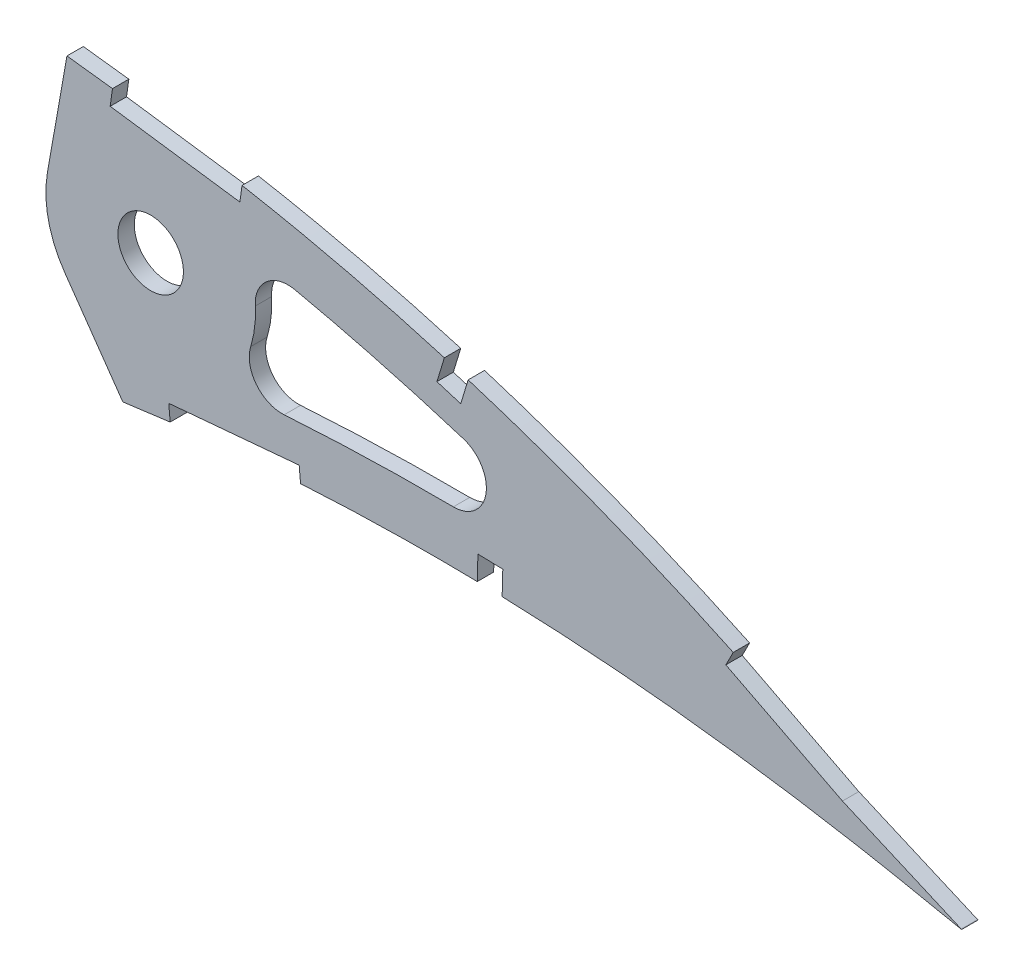
SolidWorks part; units mm, degrees
material "Pine"
ref_plane "Front Plane" through (0, 0, 0) normal (0, 0, 1) x (1, 0, 0)
ref_plane "Top Plane" through (0, 0, 0) normal (0, 1, 0) x (1, 0, 0)
ref_plane "Right Plane" through (0, 0, 0) normal (1, 0, 0) x (0, 0, -1)
curve "Curve2"
curve "Curve3"
sketch "Sketch1" plane through (0, 0, 0) normal (0, 0, 1) x (1, 0, 0)
  line L1 (519.5802, -0.8111) -> (524.4049, -1.7687)
  line L2 (520.229, 0.8111) -> (524.4049, -1.7687)
  spline S0 degree 3 poles (-2903.7635, -749.124) (66.2436, 68.8235) (-8.6937, 20.855) (1.129, -3.7148) (2.0912, -5.4642) (3.3081, -7.1386) (4.7718, -8.7374) (6.479, -10.2623) (8.428, -11.7125) (10.6162, -13.0874) (13.0406, -14.3883) (15.6982, -15.6145) (18.5868, -16.7656) (21.7032, -17.8401) (25.0435, -18.8396) (28.6046, -19.7616) (32.3825, -20.6074) (36.3735, -21.375) (40.5732, -22.065) (44.9774, -22.6771) (49.5814, -23.2117) (54.3808, -23.6676) (59.3708, -24.0458) (64.5464, -24.3466) (69.9027, -24.5709) (75.4344, -24.718) (81.1363, -24.7899) (87.003, -24.788) (93.0289, -24.7115) (99.2088, -24.5648) (105.5368, -24.3469) (112.0073, -24.0604) (118.6142, -23.7083) (125.3518, -23.2917) (132.2141, -22.8125) (139.1951, -22.2745) (146.2885, -21.679) (153.4882, -21.0296) (160.7876, -20.3295) (168.1806, -19.5808) (175.6606, -18.7872) (183.2209, -17.9512) (190.8551, -17.0772) (198.5563, -16.1668) (206.3179, -15.2253) (214.1326, -14.2544) (221.9939, -13.2579) (229.8947, -12.2404) (237.8276, -11.2019) (245.786, -10.1497) (253.7621, -9.0829) (261.7491, -8.0072) (269.7395, -6.9257) (277.7256, -5.8389) (285.7003, -4.7513) (293.6562, -3.6657) (301.5856, -2.5824) (309.4812, -1.5067) (317.3352, -0.4385) (325.1402, 0.6201) (332.8888, 1.6659) (340.5737, 2.6975) (348.187, 3.7144) (355.721, 4.7168) (363.0553, 5.6745) (370.1707, 6.6383) (377.0913, 7.4284) (383.9258, 8.1028) (390.6811, 8.6557) (397.3493, 9.0951) (403.9227, 9.4241) (410.3934, 9.6473) (416.7532, 9.7713) (422.9943, 9.7993) (429.1081, 9.7402) (435.0867, 9.5987) (440.9216, 9.3813) (446.6049, 9.0952) (452.1283, 8.7483) (457.4837, 8.3456) (462.6634, 7.8966) (467.6597, 7.4078) (472.4647, 6.8849) (477.0715, 6.3387) (481.4727, 5.7729) (485.6616, 5.1968) (489.6316, 4.6162) (493.3764, 4.0385) (496.89, 3.4693) (500.1667, 2.916) (503.2016, 2.384) (505.9892, 1.8782) (508.5257, 1.4052) (510.8062, 0.9673) (512.8275, 0.5717) (514.5859, 0.2202) (516.0789, -0.0824) (517.3037, -0.3347) (518.2586, -0.5328) (518.9417, -0.6767) (537.0698, -4.4604) (553.3394, -15.9066) (1193.1482, 2921.6684) knots -0.137857 -0.137857 -0.137857 -0.137857 0.003638 0.007293 0.011028 0.014901 0.018963 0.023258 0.027821 0.032679 0.037853 0.043362 0.049215 0.055422 0.061989 0.068918 0.076211 0.083868 0.091887 0.100266 0.109 0.118085 0.127515 0.137285 0.147388 0.157816 0.168563 0.179619 0.190977 0.202627 0.21456 0.226767 0.239236 0.251959 0.264924 0.27812 0.291536 0.30516 0.318981 0.332985 0.347163 0.361499 0.375981 0.390597 0.405333 0.420175 0.43511 0.450124 0.465203 0.480333 0.495501 0.51069 0.525887 0.541078 0.556247 0.571382 0.586466 0.601485 0.616424 0.631269 0.646007 0.660621 0.675098 0.689423 0.703582 0.716908 0.730009 0.742952 0.755726 0.76832 0.780724 0.792927 0.804916 0.816679 0.828204 0.839475 0.850481 0.861208 0.871639 0.881763 0.891564 0.901027 0.910139 0.918884 0.927249 0.935221 0.942785 0.949928 0.956638 0.962904 0.968712 0.974054 0.978918 0.983297 0.98718 0.990561 0.993433 0.995791 0.99763 0.998946 0.999737 1.102307 1.102307 1.102307 1.102307 only from (0, 0) to (519.5802, -0.8111) construction
  spline S1 degree 3 poles (2144.5607, 2521.6799) (550.9976, -26.3511) (537.2872, -9.6513) (519.6711, 1.1542) (519.0735, 1.5208) (518.237, 2.0313) (517.1622, 2.6844) (515.8486, 3.4756) (514.2969, 4.4021) (512.5075, 5.4598) (510.4807, 6.6436) (508.2172, 7.9486) (505.7172, 9.3676) (502.9816, 10.8948) (500.0114, 12.5227) (496.8072, 14.2443) (493.3701, 16.0505) (489.7015, 17.9338) (485.8019, 19.8836) (481.6733, 21.8919) (477.317, 23.9487) (472.7345, 26.0429) (467.9284, 28.1661) (462.9001, 30.305) (457.6524, 32.4505) (452.1876, 34.5902) (446.5089, 36.7144) (440.6184, 38.8094) (434.5207, 40.866) (428.2186, 42.8708) (421.7166, 44.813) (415.0186, 46.68) (408.1302, 48.4622) (401.0555, 50.1466) (393.8008, 51.7219) (386.3718, 53.1787) (378.7746, 54.5024) (371.0303, 55.692) (363.2636, 56.6815) (355.5128, 57.652) (347.7736, 58.5637) (339.9398, 59.4368) (332.019, 60.2663) (324.019, 61.0497) (315.9478, 61.7836) (307.814, 62.4658) (299.6253, 63.0925) (291.3904, 63.6628) (283.1174, 64.1714) (274.8152, 64.6183) (266.4922, 65.0001) (258.157, 65.3142) (249.8185, 65.5589) (241.4854, 65.7316) (233.1666, 65.8314) (224.8708, 65.8555) (216.6071, 65.8035) (208.384, 65.6736) (200.2107, 65.464) (192.0958, 65.1743) (184.048, 64.8046) (176.0762, 64.3519) (168.189, 63.8191) (160.3952, 63.2038) (152.7034, 62.506) (145.1216, 61.7286) (137.6583, 60.8693) (130.3214, 59.9308) (123.1191, 58.9147) (116.0593, 57.8206) (109.1496, 56.6517) (102.3976, 55.409) (95.8102, 54.0963) (89.3948, 52.714) (83.1581, 51.266) (77.1065, 49.7551) (71.2467, 48.1838) (65.5845, 46.5561) (60.1256, 44.8756) (54.8764, 43.1442) (49.8409, 41.3683) (45.0253, 39.5493) (40.4333, 37.6928) (36.0702, 35.8014) (31.9393, 33.8806) (28.0452, 31.9329) (24.3908, 29.9636) (20.9797, 27.9757) (17.8153, 25.973) (14.8987, 23.9604) (12.2341, 21.9394) (9.8224, 19.9149) (7.6651, 17.8901) (5.7652, 15.8664) (4.1228, 13.8473) (2.7399, 11.8344) (1.6168, 9.8297) (0.7561, 7.8345) (0.1568, 5.85) (-0.1712, 3.8792) (-1.2714, -22.5145) (85.5395, -42.7616) (-2987.8188, -259.5241) knots -0.109813 -0.109813 -0.109813 -0.109813 0.000254 0.001015 0.002283 0.004057 0.006331 0.009105 0.012374 0.016134 0.02038 0.025106 0.030306 0.035972 0.0421 0.048678 0.055702 0.06316 0.071046 0.07935 0.088063 0.097176 0.106678 0.116562 0.126814 0.137428 0.148394 0.1597 0.171338 0.183298 0.19557 0.208144 0.221012 0.234162 0.247587 0.261277 0.275223 0.289414 0.303771 0.317689 0.331784 0.34604 0.360444 0.374983 0.38964 0.404403 0.419257 0.434187 0.449177 0.464215 0.479284 0.49437 0.509458 0.524532 0.539579 0.554583 0.56953 0.584403 0.599191 0.613877 0.628447 0.642889 0.657186 0.671326 0.685294 0.699078 0.712665 0.726043 0.739198 0.752118 0.764792 0.777208 0.789356 0.801224 0.812804 0.824083 0.835055 0.84571 0.856038 0.866034 0.875689 0.884998 0.893953 0.902553 0.910789 0.918661 0.926166 0.933303 0.940071 0.946475 0.952518 0.958205 0.963547 0.968557 0.97325 0.977651 0.981787 0.985694 0.989415 0.993001 0.996508 1.132043 1.132043 1.132043 1.132043 only from (520.229, 0.8111) to (0, 0) construction
  spline S2 degree 3 poles (0, 0) (0.1336, -0.6306) (0.4014, -1.8948) (1.129, -3.7148) (2.0912, -5.4642) (3.3081, -7.1386) (4.7718, -8.7374) (6.479, -10.2623) (8.428, -11.7125) (10.6162, -13.0874) (13.0406, -14.3883) (15.6982, -15.6145) (18.5868, -16.7656) (21.7032, -17.8401) (25.0435, -18.8396) (28.6046, -19.7616) (32.3825, -20.6074) (36.3735, -21.375) (40.5732, -22.065) (44.9774, -22.6771) (49.5814, -23.2117) (54.3808, -23.6676) (59.3708, -24.0458) (64.5464, -24.3466) (69.9027, -24.5709) (75.4344, -24.718) (81.1363, -24.7899) (87.003, -24.788) (93.0289, -24.7115) (99.2088, -24.5648) (105.5368, -24.3469) (112.0073, -24.0604) (118.6142, -23.7083) (125.3518, -23.2917) (132.2141, -22.8125) (139.1951, -22.2745) (146.2885, -21.679) (153.4882, -21.0296) (160.7876, -20.3295) (168.1806, -19.5808) (175.6606, -18.7872) (183.2209, -17.9512) (190.8551, -17.0772) (198.5563, -16.1668) (206.3179, -15.2253) (214.1326, -14.2544) (221.9939, -13.2579) (229.8947, -12.2404) (237.8276, -11.2019) (245.786, -10.1497) (253.7621, -9.0829) (261.7491, -8.0072) (269.7395, -6.9257) (277.7256, -5.8389) (285.7003, -4.7513) (293.6562, -3.6657) (301.5856, -2.5824) (309.4812, -1.5067) (317.3352, -0.4385) (325.1402, 0.6201) (332.8888, 1.6659) (340.5737, 2.6975) (348.187, 3.7144) (355.721, 4.7168) (363.0553, 5.6745) (370.1707, 6.6383) (377.0913, 7.4284) (383.9258, 8.1028) (390.6811, 8.6557) (397.3493, 9.0951) (403.9227, 9.4241) (410.3934, 9.6473) (416.7532, 9.7713) (422.9943, 9.7993) (429.1081, 9.7402) (435.0867, 9.5987) (440.9216, 9.3813) (446.6049, 9.0952) (452.1283, 8.7483) (457.4837, 8.3456) (462.6634, 7.8966) (467.6597, 7.4078) (472.4647, 6.8849) (477.0715, 6.3387) (481.4727, 5.7729) (485.6616, 5.1968) (489.6316, 4.6162) (493.3764, 4.0385) (496.89, 3.4693) (500.1667, 2.916) (503.2016, 2.384) (505.9892, 1.8782) (508.5257, 1.4052) (510.8062, 0.9673) (512.8275, 0.5717) (514.5859, 0.2202) (516.0789, -0.0824) (517.3037, -0.3347) (518.2586, -0.5328) (518.9417, -0.6767) (519.3522, -0.7624) (519.5346, -0.8013) (519.5802, -0.8111) knots 0 0 0 0 0.003638 0.007293 0.011028 0.014901 0.018963 0.023258 0.027821 0.032679 0.037853 0.043362 0.049215 0.055422 0.061989 0.068918 0.076211 0.083868 0.091887 0.100266 0.109 0.118085 0.127515 0.137285 0.147388 0.157816 0.168563 0.179619 0.190977 0.202627 0.21456 0.226767 0.239236 0.251959 0.264924 0.27812 0.291536 0.30516 0.318981 0.332985 0.347163 0.361499 0.375981 0.390597 0.405333 0.420175 0.43511 0.450124 0.465203 0.480333 0.495501 0.51069 0.525887 0.541078 0.556247 0.571382 0.586466 0.601485 0.616424 0.631269 0.646007 0.660621 0.675098 0.689423 0.703582 0.716908 0.730009 0.742952 0.755726 0.76832 0.780724 0.792927 0.804916 0.816679 0.828204 0.839475 0.850481 0.861208 0.871639 0.881763 0.891564 0.901027 0.910139 0.918884 0.927249 0.935221 0.942785 0.949928 0.956638 0.962904 0.968712 0.974054 0.978918 0.983297 0.98718 0.990561 0.993433 0.995791 0.99763 0.998946 0.999737 1 1 1 1
  spline S3 degree 3 poles (520.229, 0.8111) (520.1892, 0.8357) (520.0299, 0.9341) (519.6711, 1.1542) (519.0735, 1.5208) (518.237, 2.0313) (517.1622, 2.6844) (515.8486, 3.4756) (514.2969, 4.4021) (512.5075, 5.4598) (510.4807, 6.6436) (508.2172, 7.9486) (505.7172, 9.3676) (502.9816, 10.8948) (500.0114, 12.5227) (496.8072, 14.2443) (493.3701, 16.0505) (489.7015, 17.9338) (485.8019, 19.8836) (481.6733, 21.8919) (477.317, 23.9487) (472.7345, 26.0429) (467.9284, 28.1661) (462.9001, 30.305) (457.6524, 32.4505) (452.1876, 34.5902) (446.5089, 36.7144) (440.6184, 38.8094) (434.5207, 40.866) (428.2186, 42.8708) (421.7166, 44.813) (415.0186, 46.68) (408.1302, 48.4622) (401.0555, 50.1466) (393.8008, 51.7219) (386.3718, 53.1787) (378.7746, 54.5024) (371.0303, 55.692) (363.2636, 56.6815) (355.5128, 57.652) (347.7736, 58.5637) (339.9398, 59.4368) (332.019, 60.2663) (324.019, 61.0497) (315.9478, 61.7836) (307.814, 62.4658) (299.6253, 63.0925) (291.3904, 63.6628) (283.1174, 64.1714) (274.8152, 64.6183) (266.4922, 65.0001) (258.157, 65.3142) (249.8185, 65.5589) (241.4854, 65.7316) (233.1666, 65.8314) (224.8708, 65.8555) (216.6071, 65.8035) (208.384, 65.6736) (200.2107, 65.464) (192.0958, 65.1743) (184.048, 64.8046) (176.0762, 64.3519) (168.189, 63.8191) (160.3952, 63.2038) (152.7034, 62.506) (145.1216, 61.7286) (137.6583, 60.8693) (130.3214, 59.9308) (123.1191, 58.9147) (116.0593, 57.8206) (109.1496, 56.6517) (102.3976, 55.409) (95.8102, 54.0963) (89.3948, 52.714) (83.1581, 51.266) (77.1065, 49.7551) (71.2467, 48.1838) (65.5845, 46.5561) (60.1256, 44.8756) (54.8764, 43.1442) (49.8409, 41.3683) (45.0253, 39.5493) (40.4333, 37.6928) (36.0702, 35.8014) (31.9393, 33.8806) (28.0452, 31.9329) (24.3908, 29.9636) (20.9797, 27.9757) (17.8153, 25.973) (14.8987, 23.9604) (12.2341, 21.9394) (9.8224, 19.9149) (7.6651, 17.8901) (5.7652, 15.8664) (4.1228, 13.8473) (2.7399, 11.8344) (1.6168, 9.8297) (0.7561, 7.8345) (0.1568, 5.85) (-0.1712, 3.8792) (-0.2528, 1.9205) (-0.0842, 0.6392) (0, 0) knots 0 0 0 0 0.000254 0.001015 0.002283 0.004057 0.006331 0.009105 0.012374 0.016134 0.02038 0.025106 0.030306 0.035972 0.0421 0.048678 0.055702 0.06316 0.071046 0.07935 0.088063 0.097176 0.106678 0.116562 0.126814 0.137428 0.148394 0.1597 0.171338 0.183298 0.19557 0.208144 0.221012 0.234162 0.247587 0.261277 0.275223 0.289414 0.303771 0.317689 0.331784 0.34604 0.360444 0.374983 0.38964 0.404403 0.419257 0.434187 0.449177 0.464215 0.479284 0.49437 0.509458 0.524532 0.539579 0.554583 0.56953 0.584403 0.599191 0.613877 0.628447 0.642889 0.657186 0.671326 0.685294 0.699078 0.712665 0.726043 0.739198 0.752118 0.764792 0.777208 0.789356 0.801224 0.812804 0.824083 0.835055 0.84571 0.856038 0.866034 0.875689 0.884998 0.893953 0.902553 0.910789 0.918661 0.926166 0.933303 0.940071 0.946475 0.952518 0.958205 0.963547 0.968557 0.97325 0.977651 0.981787 0.985694 0.989415 0.993001 0.996508 1 1 1 1
extrude "Boss-Extrude1" add sketch "Sketch1" along normal blind 3.175
sketch "Sketch4" plane through (0, 0, 0) normal (0, 0, -1) x (-1, 0, 0)
  line L0 (-347.1309, 36.7611) -> (-350.9097, 58.1919)
  line L1 (-350.497, 21.5775) -> (-361.7496, 5.5072)
  line L2 (-367.1422, 33.2326) -> (-406.863, 33.2326)
  circle A0 centre (-367.1422, 33.2326) radius 20.32
  circle A1 centre (-367.1422, 33.2326) radius 6.35
  spline S2 degree 3 poles (1939.7558, -484.7932) (-49.4812, 57.6608) (7.5449, 17.9816) (-1.129, -3.7148) (-2.0912, -5.4642) (-3.3081, -7.1386) (-4.7718, -8.7374) (-6.479, -10.2623) (-8.428, -11.7125) (-10.6162, -13.0874) (-13.0406, -14.3883) (-15.6982, -15.6145) (-18.5868, -16.7656) (-21.7032, -17.8401) (-25.0435, -18.8396) (-28.6046, -19.7616) (-32.3825, -20.6074) (-36.3735, -21.375) (-40.5732, -22.065) (-44.9774, -22.6771) (-49.5814, -23.2117) (-54.3808, -23.6676) (-59.3708, -24.0458) (-64.5464, -24.3466) (-69.9027, -24.5709) (-75.4344, -24.718) (-81.1363, -24.7899) (-87.003, -24.788) (-93.0289, -24.7115) (-99.2088, -24.5648) (-105.5368, -24.3469) (-112.0073, -24.0604) (-118.6142, -23.7083) (-125.3518, -23.2917) (-132.2141, -22.8125) (-139.1951, -22.2745) (-146.2885, -21.679) (-153.4882, -21.0296) (-160.7876, -20.3295) (-168.1806, -19.5808) (-175.6606, -18.7872) (-183.2209, -17.9512) (-190.8551, -17.0772) (-198.5563, -16.1668) (-206.3179, -15.2253) (-214.1326, -14.2544) (-221.9939, -13.2579) (-229.8947, -12.2404) (-237.8276, -11.2019) (-245.786, -10.1497) (-253.7621, -9.0829) (-261.7491, -8.0072) (-269.7395, -6.9257) (-277.7256, -5.8389) (-285.7003, -4.7513) (-293.6562, -3.6657) (-301.5856, -2.5824) (-309.4812, -1.5067) (-317.3352, -0.4385) (-325.1402, 0.6201) (-332.8888, 1.6659) (-340.5737, 2.6975) (-348.187, 3.7144) (-355.721, 4.7168) (-363.0553, 5.6745) (-370.1707, 6.6383) (-377.0913, 7.4284) (-383.9258, 8.1028) (-390.6811, 8.6557) (-397.3493, 9.0951) (-403.9227, 9.4241) (-410.3934, 9.6473) (-416.7532, 9.7713) (-422.9943, 9.7993) (-429.1081, 9.7402) (-435.0867, 9.5987) (-440.9216, 9.3813) (-446.6049, 9.0952) (-452.1283, 8.7483) (-457.4837, 8.3456) (-462.6634, 7.8966) (-467.6597, 7.4078) (-472.4647, 6.8849) (-477.0715, 6.3387) (-481.4727, 5.7729) (-485.6616, 5.1968) (-489.6316, 4.6162) (-493.3764, 4.0385) (-496.89, 3.4693) (-500.1667, 2.916) (-503.2016, 2.384) (-505.9892, 1.8782) (-508.5257, 1.4052) (-510.8062, 0.9673) (-512.8275, 0.5717) (-514.5859, 0.2202) (-516.0789, -0.0824) (-517.3037, -0.3347) (-518.2586, -0.5328) (-518.9417, -0.6767) (-534.8295, -3.9928) (-549.2415, -13.1623) (-979.5797, 1945.0117) knots -0.120445 -0.120445 -0.120445 -0.120445 0.003638 0.007293 0.011028 0.014901 0.018963 0.023258 0.027821 0.032679 0.037853 0.043362 0.049215 0.055422 0.061989 0.068918 0.076211 0.083868 0.091887 0.100266 0.109 0.118085 0.127515 0.137285 0.147388 0.157816 0.168563 0.179619 0.190977 0.202627 0.21456 0.226767 0.239236 0.251959 0.264924 0.27812 0.291536 0.30516 0.318981 0.332985 0.347163 0.361499 0.375981 0.390597 0.405333 0.420175 0.43511 0.450124 0.465203 0.480333 0.495501 0.51069 0.525887 0.541078 0.556247 0.571382 0.586466 0.601485 0.616424 0.631269 0.646007 0.660621 0.675098 0.689423 0.703582 0.716908 0.730009 0.742952 0.755726 0.76832 0.780724 0.792927 0.804916 0.816679 0.828204 0.839475 0.850481 0.861208 0.871639 0.881763 0.891564 0.901027 0.910139 0.918884 0.927249 0.935221 0.942785 0.949928 0.956638 0.962904 0.968712 0.974054 0.978918 0.983297 0.98718 0.990561 0.993433 0.995791 0.99763 0.998946 0.999737 1.089371 1.089371 1.089371 1.089371 only from (0, 0) to (-519.5802, -0.8111) construction
  spline S3 degree 3 poles (-1613.7482, 1674.6901) (-547.5042, -22.2613) (-535.1053, -8.313) (-519.6711, 1.1542) (-519.0735, 1.5208) (-518.237, 2.0313) (-517.1622, 2.6844) (-515.8486, 3.4756) (-514.2969, 4.4021) (-512.5075, 5.4598) (-510.4807, 6.6436) (-508.2172, 7.9486) (-505.7172, 9.3676) (-502.9816, 10.8948) (-500.0114, 12.5227) (-496.8072, 14.2443) (-493.3701, 16.0505) (-489.7015, 17.9338) (-485.8019, 19.8836) (-481.6733, 21.8919) (-477.317, 23.9487) (-472.7345, 26.0429) (-467.9284, 28.1661) (-462.9001, 30.305) (-457.6524, 32.4505) (-452.1876, 34.5902) (-446.5089, 36.7144) (-440.6184, 38.8094) (-434.5207, 40.866) (-428.2186, 42.8708) (-421.7166, 44.813) (-415.0186, 46.68) (-408.1302, 48.4622) (-401.0555, 50.1466) (-393.8008, 51.7219) (-386.3718, 53.1787) (-378.7746, 54.5024) (-371.0303, 55.692) (-363.2636, 56.6815) (-355.5128, 57.652) (-347.7736, 58.5637) (-339.9398, 59.4368) (-332.019, 60.2663) (-324.019, 61.0497) (-315.9478, 61.7836) (-307.814, 62.4658) (-299.6253, 63.0925) (-291.3904, 63.6628) (-283.1174, 64.1714) (-274.8152, 64.6183) (-266.4922, 65.0001) (-258.157, 65.3142) (-249.8185, 65.5589) (-241.4854, 65.7316) (-233.1666, 65.8314) (-224.8708, 65.8555) (-216.6071, 65.8035) (-208.384, 65.6736) (-200.2107, 65.464) (-192.0958, 65.1743) (-184.048, 64.8046) (-176.0762, 64.3519) (-168.189, 63.8191) (-160.3952, 63.2038) (-152.7034, 62.506) (-145.1216, 61.7286) (-137.6583, 60.8693) (-130.3214, 59.9308) (-123.1191, 58.9147) (-116.0593, 57.8206) (-109.1496, 56.6517) (-102.3976, 55.409) (-95.8102, 54.0963) (-89.3948, 52.714) (-83.1581, 51.266) (-77.1065, 49.7551) (-71.2467, 48.1838) (-65.5845, 46.5561) (-60.1256, 44.8756) (-54.8764, 43.1442) (-49.8409, 41.3683) (-45.0253, 39.5493) (-40.4333, 37.6928) (-36.0702, 35.8014) (-31.9393, 33.8806) (-28.0452, 31.9329) (-24.3908, 29.9636) (-20.9797, 27.9757) (-17.8153, 25.973) (-14.8987, 23.9604) (-12.2341, 21.9394) (-9.8224, 19.9149) (-7.6651, 17.8901) (-5.7652, 15.8664) (-4.1228, 13.8473) (-2.7399, 11.8344) (-1.6168, 9.8297) (-0.7561, 7.8345) (-0.1568, 5.85) (0.1712, 3.8792) (1.1427, -19.4272) (-65.9725, -37.8239) (1990.4087, -188.0581) knots -0.095928 -0.095928 -0.095928 -0.095928 0.000254 0.001015 0.002283 0.004057 0.006331 0.009105 0.012374 0.016134 0.02038 0.025106 0.030306 0.035972 0.0421 0.048678 0.055702 0.06316 0.071046 0.07935 0.088063 0.097176 0.106678 0.116562 0.126814 0.137428 0.148394 0.1597 0.171338 0.183298 0.19557 0.208144 0.221012 0.234162 0.247587 0.261277 0.275223 0.289414 0.303771 0.317689 0.331784 0.34604 0.360444 0.374983 0.38964 0.404403 0.419257 0.434187 0.449177 0.464215 0.479284 0.49437 0.509458 0.524532 0.539579 0.554583 0.56953 0.584403 0.599191 0.613877 0.628447 0.642889 0.657186 0.671326 0.685294 0.699078 0.712665 0.726043 0.739198 0.752118 0.764792 0.777208 0.789356 0.801224 0.812804 0.824083 0.835055 0.84571 0.856038 0.866034 0.875689 0.884998 0.893953 0.902553 0.910789 0.918661 0.926166 0.933303 0.940071 0.946475 0.952518 0.958205 0.963547 0.968557 0.97325 0.977651 0.981787 0.985694 0.989415 0.993001 0.996508 1.11536 1.11536 1.11536 1.11536 only from (-520.229, 0.8111) to (0, 0) construction
  spline S4 degree 3 poles (-1978.354, 2157.5892) (159.6529, 858.6126) (-7.0413, 13.2519) (-10.1565, 1.1414) (-10.167, 1.1042) (-10.1763, 1.0725) (-10.1781, 1.0668) (-10.1835, 1.0497) (-10.1867, 1.0399) (-10.2052, 0.985) (-10.2286, 0.9219) (-10.2791, 0.8017) (-10.2985, 0.7574) (-10.3426, 0.661) (-10.3676, 0.6085) (-10.4428, 0.4561) (-10.496, 0.3558) (-10.6081, 0.1584) (-10.6662, 0.0627) (-10.855, -0.2291) (-11.0064, -0.4384) (-11.5378, -1.0936) (-11.9971, -1.5677) (-13.099, -2.5256) (-13.7412, -3.01) (-15.1702, -3.9568) (-15.9588, -4.4208) (-17.636, -5.3094) (-18.5262, -5.7351) (-21.3094, -6.9503) (-23.3073, -7.6749) (-27.467, -8.9758) (-29.6229, -9.5497) (-34.0316, -10.5753) (-36.2795, -11.0252) (-40.839, -11.8243) (-43.1471, -12.1728) (-47.8035, -12.7862) (-50.1501, -13.0508) (-57.2292, -13.7373) (-62.003, -14.0541) (-71.5985, -14.4809) (-76.422, -14.5891) (-83.6816, -14.6324) (-86.1037, -14.6268) (-90.9551, -14.5789) (-93.3856, -14.5371) (-100.6793, -14.3647) (-105.548, -14.1854) (-120.1773, -13.4939) (-129.9476, -12.83) (-149.5009, -11.2301) (-159.287, -10.2936) (-178.863, -8.2392) (-188.6532, -7.1203) (-203.3458, -5.3542) (-208.2424, -4.7511) (-218.0387, -3.5207) (-222.9395, -2.8943) (-232.7359, -1.6243) (-237.6385, -0.9795) (-247.4393, 0.3202) (-252.3404, 0.9774) (-262.147, 2.2986) (-267.05, 2.9625) (-276.8577, 4.2964) (-281.7641, 4.9659) (-291.5768, 6.3047) (-296.4825, 6.9752) (-306.3007, 8.3142) (-311.2087, 8.9822) (-325.9378, 10.9826) (-335.766, 12.3068) (-348.0467, 13.9451) (-350.5039, 14.2725) (-354.1964, 14.7609) (-355.4285, 14.923) (-357.8843, 15.2457) (-359.1092, 15.4066) (-361.5526, 15.7296) (-362.7689, 15.8922) (-365.2348, 16.221) (-366.4798, 16.3859) (-368.3663, 16.6273) (-368.9995, 16.7068) (-371.53, 17.0174) (-373.424, 17.2342) (-377.8329, 17.7104) (-380.3527, 17.9617) (-385.4072, 18.4196) (-387.9354, 18.6255) (-395.5221, 19.1767) (-400.5883, 19.4552) (-408.19, 19.7386) (-410.7237, 19.8108) (-415.7936, 19.9113) (-418.3301, 19.9392) (-425.9339, 19.9566) (-431.0019, 19.8815) (-441.1324, 19.5579) (-446.1907, 19.3102) (-453.7725, 18.8139) (-456.2982, 18.6271) (-775.6257, -7.5609) (-1062.3017, -351.5368) (-2984.1092, -1609.9578) knots -0.216436 -0.216436 -0.216436 -0.216436 0.001953 0.001953 0.00293 0.00293 0.003418 0.003418 0.003906 0.003906 0.005859 0.005859 0.006836 0.006836 0.007813 0.007813 0.009766 0.009766 0.011719 0.011719 0.015625 0.015625 0.023438 0.023438 0.03125 0.03125 0.039063 0.039063 0.046875 0.046875 0.0625 0.0625 0.078125 0.078125 0.09375 0.09375 0.109375 0.109375 0.125 0.125 0.15625 0.15625 0.1875 0.1875 0.203125 0.203125 0.21875 0.21875 0.25 0.25 0.3125 0.3125 0.375 0.375 0.4375 0.4375 0.46875 0.46875 0.5 0.5 0.53125 0.53125 0.5625 0.5625 0.59375 0.59375 0.625 0.625 0.65625 0.65625 0.6875 0.6875 0.75 0.75 0.765625 0.765625 0.773438 0.773438 0.78125 0.78125 0.789063 0.789063 0.796875 0.796875 0.800781 0.800781 0.8125 0.8125 0.828125 0.828125 0.84375 0.84375 0.875 0.875 0.890625 0.890625 0.90625 0.90625 0.9375 0.9375 0.96875 0.96875 0.984375 0.984375 2.947098 2.947098 2.947098 2.947098 only from (-10.022, 1.7185) to (-466.3815, 17.739)
  spline S5 degree 3 poles (-2960.1923, -1647.6146) (-778.0163, -316.2747) (-661.2066, -63.7231) (-457.1185, 21.6971) (-454.7864, 22.6463) (-450.1039, 24.4978) (-447.7524, 25.4007) (-443.0352, 27.1579) (-440.669, 28.0121) (-428.7885, 32.1652) (-419.1573, 35.0991) (-404.5516, 38.8923) (-399.6593, 40.0545) (-392.2853, 41.6432) (-389.8214, 42.1473) (-384.8862, 43.1026) (-382.4148, 43.5535) (-377.456, 44.4051) (-374.9691, 44.8071) (-371.8706, 45.272) (-371.2512, 45.3631) (-370.0129, 45.5414) (-369.3949, 45.6283) (-367.531, 45.885) (-365.6514, 46.1331) (-363.7495, 46.3759) (-362.4766, 46.5374) (-361.8369, 46.6182) (-359.9197, 46.8599) (-358.6437, 47.0199) (-354.8218, 47.4941) (-352.2828, 47.8012) (-347.1922, 48.3982) (-344.6438, 48.6888) (-339.5477, 49.2537) (-336.9993, 49.5279) (-329.3512, 50.3256) (-324.2496, 50.8242) (-308.9368, 52.2174) (-298.7176, 53.0107) (-278.2717, 54.3039) (-268.0406, 54.8057) (-247.5801, 55.4913) (-237.3501, 55.6755) (-216.9004, 55.6922) (-206.6831, 55.5256) (-191.3779, 54.9785) (-186.2812, 54.7472) (-176.0979, 54.177) (-171.0099, 53.8396) (-160.8533, 53.0504) (-155.7814, 52.598) (-145.6574, 51.572) (-140.6072, 50.9971) (-125.4892, 49.071) (-115.4646, 47.5214) (-100.5547, 44.7064) (-95.6096, 43.687) (-85.777, 41.462) (-80.8922, 40.2578) (-71.2072, 37.6367) (-66.4068, 36.2209) (-59.3024, 33.909) (-56.9474, 33.1063) (-52.2821, 31.4343) (-49.9693, 30.5636) (-45.3927, 28.7458) (-43.1318, 27.7996) (-38.6715, 25.8196) (-36.476, 24.7882) (-32.1758, 22.6281) (-30.0692, 21.4995) (-27.0125, 19.7284) (-26.0103, 19.1247) (-24.0464, 17.889) (-23.0831, 17.2561) (-21.2128, 15.9659) (-20.3049, 15.3076) (-18.5534, 13.9629) (-17.7093, 13.2763) (-16.1081, 11.8824) (-15.3519, 11.176) (-14.3045, 10.1109) (-13.9701, 9.7552) (-13.3325, 9.0431) (-13.0296, 8.687) (-12.1803, 7.6299) (-11.6896, 6.9348) (-10.8906, 5.6128) (-10.5874, 4.9936) (-10.269, 4.158) (-10.1861, 3.8969) (-10.0953, 3.5459) (-10.0707, 3.4366) (-10.0267, 3.2104) (-10.0081, 3.096) (-9.9777, 2.8649) (-9.9658, 2.7438) (-9.9529, 2.5547) (-9.9512, 2.4811) (-9.9516, 2.4178) (-9.9518, 2.4066) (-9.9523, 2.387) (-9.9526, 2.38) (-9.9538, 2.3538) (-9.956, 2.318) (-10.9137, -8.9231) (-124.2495, -805.3826) (-2616.8841, -1329.8892) knots -1.341255 -1.341255 -1.341255 -1.341255 0.015625 0.015625 0.03125 0.03125 0.046875 0.046875 0.0625 0.0625 0.125 0.125 0.15625 0.15625 0.171875 0.171875 0.1875 0.1875 0.203125 0.203125 0.207031 0.207031 0.210937 0.210937 0.21875 0.222656 0.222656 0.226562 0.226562 0.234375 0.234375 0.25 0.25 0.265625 0.265625 0.28125 0.28125 0.3125 0.3125 0.375 0.375 0.4375 0.4375 0.5 0.5 0.5625 0.5625 0.59375 0.59375 0.625 0.625 0.65625 0.65625 0.6875 0.6875 0.75 0.75 0.78125 0.78125 0.8125 0.8125 0.84375 0.84375 0.859375 0.859375 0.875 0.875 0.890625 0.890625 0.90625 0.90625 0.921875 0.921875 0.929688 0.929688 0.9375 0.9375 0.945313 0.945313 0.953125 0.953125 0.960938 0.960938 0.964844 0.964844 0.96875 0.96875 0.976563 0.976563 0.984375 0.984375 0.988281 0.988281 0.990234 0.990234 0.992188 0.992188 0.994141 0.994141 0.996094 0.996094 0.996582 0.996582 0.99707 0.99707 0.998047 0.998047 1.199641 1.199641 1.199641 1.199641 only from (-466.3815, 17.739) to (-10.022, 1.7185)
  spline S6 degree 3 poles (-10.022, 1.7185) (-10.0741, 1.4777) (-10.1149, 1.3032) (-10.1565, 1.1414) (-10.167, 1.1042) (-10.1763, 1.0725) (-10.1781, 1.0668) (-10.1835, 1.0497) (-10.1867, 1.0399) (-10.2052, 0.985) (-10.2286, 0.9219) (-10.2791, 0.8017) (-10.2985, 0.7574) (-10.3426, 0.661) (-10.3676, 0.6085) (-10.4428, 0.4561) (-10.496, 0.3558) (-10.6081, 0.1584) (-10.6662, 0.0627) (-10.855, -0.2291) (-11.0064, -0.4384) (-11.5378, -1.0936) (-11.9971, -1.5677) (-13.099, -2.5256) (-13.7412, -3.01) (-15.1702, -3.9568) (-15.9588, -4.4208) (-17.636, -5.3094) (-18.5262, -5.7351) (-21.3094, -6.9503) (-23.3073, -7.6749) (-27.467, -8.9758) (-29.6229, -9.5497) (-34.0316, -10.5753) (-36.2795, -11.0252) (-40.839, -11.8243) (-43.1471, -12.1728) (-47.8035, -12.7862) (-50.1501, -13.0508) (-57.2292, -13.7373) (-62.003, -14.0541) (-71.5985, -14.4809) (-76.422, -14.5891) (-83.6816, -14.6324) (-86.1037, -14.6268) (-90.9551, -14.5789) (-93.3856, -14.5371) (-100.6793, -14.3647) (-105.548, -14.1854) (-120.1773, -13.4939) (-129.9476, -12.83) (-149.5009, -11.2301) (-159.287, -10.2936) (-178.863, -8.2392) (-188.6532, -7.1203) (-203.3458, -5.3542) (-208.2424, -4.7511) (-218.0387, -3.5207) (-222.9395, -2.8943) (-232.7359, -1.6243) (-237.6385, -0.9795) (-247.4393, 0.3202) (-252.3404, 0.9774) (-262.147, 2.2986) (-267.05, 2.9625) (-276.8577, 4.2964) (-281.7641, 4.9659) (-291.5768, 6.3047) (-296.4825, 6.9752) (-306.3007, 8.3142) (-311.2087, 8.9822) (-325.9378, 10.9826) (-335.766, 12.3068) (-348.0467, 13.9451) (-350.5039, 14.2725) (-354.1964, 14.7609) (-355.4285, 14.923) (-357.8843, 15.2457) (-359.1092, 15.4066) (-361.5526, 15.7296) (-362.7689, 15.8922) (-365.2348, 16.221) (-366.4798, 16.3859) (-368.3663, 16.6273) (-368.9995, 16.7068) (-371.53, 17.0174) (-373.424, 17.2342) (-377.8329, 17.7104) (-380.3527, 17.9617) (-385.4072, 18.4196) (-387.9354, 18.6255) (-395.5221, 19.1767) (-400.5883, 19.4552) (-408.19, 19.7386) (-410.7237, 19.8108) (-415.7936, 19.9113) (-418.3301, 19.9392) (-425.9339, 19.9566) (-431.0019, 19.8815) (-441.1324, 19.5579) (-446.1907, 19.3102) (-453.7725, 18.8139) (-456.2982, 18.6271) (-461.3423, 18.2134) (-463.8625, 17.9865) (-466.3815, 17.739) knots 0 0 0 0 0.001953 0.001953 0.00293 0.00293 0.003418 0.003418 0.003906 0.003906 0.005859 0.005859 0.006836 0.006836 0.007813 0.007813 0.009766 0.009766 0.011719 0.011719 0.015625 0.015625 0.023438 0.023438 0.03125 0.03125 0.039063 0.039063 0.046875 0.046875 0.0625 0.0625 0.078125 0.078125 0.09375 0.09375 0.109375 0.109375 0.125 0.125 0.15625 0.15625 0.1875 0.1875 0.203125 0.203125 0.21875 0.21875 0.25 0.25 0.3125 0.3125 0.375 0.375 0.4375 0.4375 0.46875 0.46875 0.5 0.5 0.53125 0.53125 0.5625 0.5625 0.59375 0.59375 0.625 0.625 0.65625 0.65625 0.6875 0.6875 0.75 0.75 0.765625 0.765625 0.773438 0.773438 0.78125 0.78125 0.789063 0.789063 0.796875 0.796875 0.800781 0.800781 0.8125 0.8125 0.828125 0.828125 0.84375 0.84375 0.875 0.875 0.890625 0.890625 0.90625 0.90625 0.9375 0.9375 0.96875 0.96875 0.984375 0.984375 1 1 1 1
  spline S7 degree 3 poles (-466.3815, 17.739) (-464.0774, 18.7574) (-461.7652, 19.7522) (-457.1185, 21.6971) (-454.7864, 22.6463) (-450.1039, 24.4978) (-447.7524, 25.4007) (-443.0352, 27.1579) (-440.669, 28.0121) (-428.7885, 32.1652) (-419.1573, 35.0991) (-404.5516, 38.8923) (-399.6593, 40.0545) (-392.2853, 41.6432) (-389.8214, 42.1473) (-384.8862, 43.1026) (-382.4148, 43.5535) (-377.456, 44.4051) (-374.9691, 44.8071) (-371.8706, 45.272) (-371.2512, 45.3631) (-370.0129, 45.5414) (-369.3949, 45.6283) (-367.531, 45.885) (-365.6514, 46.1331) (-363.7495, 46.3759) (-362.4766, 46.5374) (-361.8369, 46.6182) (-359.9197, 46.8599) (-358.6437, 47.0199) (-354.8218, 47.4941) (-352.2828, 47.8012) (-347.1922, 48.3982) (-344.6438, 48.6888) (-339.5477, 49.2537) (-336.9993, 49.5279) (-329.3512, 50.3256) (-324.2496, 50.8242) (-308.9368, 52.2174) (-298.7176, 53.0107) (-278.2717, 54.3039) (-268.0406, 54.8057) (-247.5801, 55.4913) (-237.3501, 55.6755) (-216.9004, 55.6922) (-206.6831, 55.5256) (-191.3779, 54.9785) (-186.2812, 54.7472) (-176.0979, 54.177) (-171.0099, 53.8396) (-160.8533, 53.0504) (-155.7814, 52.598) (-145.6574, 51.572) (-140.6072, 50.9971) (-125.4892, 49.071) (-115.4646, 47.5214) (-100.5547, 44.7064) (-95.6096, 43.687) (-85.777, 41.462) (-80.8922, 40.2578) (-71.2072, 37.6367) (-66.4068, 36.2209) (-59.3024, 33.909) (-56.9474, 33.1063) (-52.2821, 31.4343) (-49.9693, 30.5636) (-45.3927, 28.7458) (-43.1318, 27.7996) (-38.6715, 25.8196) (-36.476, 24.7882) (-32.1758, 22.6281) (-30.0692, 21.4995) (-27.0125, 19.7284) (-26.0103, 19.1247) (-24.0464, 17.889) (-23.0831, 17.2561) (-21.2128, 15.9659) (-20.3049, 15.3076) (-18.5534, 13.9629) (-17.7093, 13.2763) (-16.1081, 11.8824) (-15.3519, 11.176) (-14.3045, 10.1109) (-13.9701, 9.7552) (-13.3325, 9.0431) (-13.0296, 8.687) (-12.1803, 7.6299) (-11.6896, 6.9348) (-10.8906, 5.6128) (-10.5874, 4.9936) (-10.269, 4.158) (-10.1861, 3.8969) (-10.0953, 3.5459) (-10.0707, 3.4366) (-10.0267, 3.2104) (-10.0081, 3.096) (-9.9777, 2.8649) (-9.9658, 2.7438) (-9.9529, 2.5547) (-9.9512, 2.4811) (-9.9516, 2.4178) (-9.9518, 2.4066) (-9.9523, 2.387) (-9.9526, 2.38) (-9.9538, 2.3538) (-9.956, 2.318) (-9.9698, 2.1554) (-9.9896, 1.9733) (-10.022, 1.7185) knots 0 0 0 0 0.015625 0.015625 0.03125 0.03125 0.046875 0.046875 0.0625 0.0625 0.125 0.125 0.15625 0.15625 0.171875 0.171875 0.1875 0.1875 0.203125 0.203125 0.207031 0.207031 0.210937 0.210937 0.21875 0.222656 0.222656 0.226562 0.226562 0.234375 0.234375 0.25 0.25 0.265625 0.265625 0.28125 0.28125 0.3125 0.3125 0.375 0.375 0.4375 0.4375 0.5 0.5 0.5625 0.5625 0.59375 0.59375 0.625 0.625 0.65625 0.65625 0.6875 0.6875 0.75 0.75 0.78125 0.78125 0.8125 0.8125 0.84375 0.84375 0.859375 0.859375 0.875 0.875 0.890625 0.890625 0.90625 0.90625 0.921875 0.921875 0.929688 0.929688 0.9375 0.9375 0.945313 0.945313 0.953125 0.953125 0.960938 0.960938 0.964844 0.964844 0.96875 0.96875 0.976563 0.976563 0.984375 0.984375 0.988281 0.988281 0.990234 0.990234 0.992188 0.992188 0.994141 0.994141 0.996094 0.996094 0.996582 0.996582 0.99707 0.99707 0.998047 0.998047 1 1 1 1
  spline S8 degree 3 poles (0, 0) (-0.1336, -0.6306) (-0.4014, -1.8948) (-1.129, -3.7148) (-2.0912, -5.4642) (-3.3081, -7.1386) (-4.7718, -8.7374) (-6.479, -10.2623) (-8.428, -11.7125) (-10.6162, -13.0874) (-13.0406, -14.3883) (-15.6982, -15.6145) (-18.5868, -16.7656) (-21.7032, -17.8401) (-25.0435, -18.8396) (-28.6046, -19.7616) (-32.3825, -20.6074) (-36.3735, -21.375) (-40.5732, -22.065) (-44.9774, -22.6771) (-49.5814, -23.2117) (-54.3808, -23.6676) (-59.3708, -24.0458) (-64.5464, -24.3466) (-69.9027, -24.5709) (-75.4344, -24.718) (-81.1363, -24.7899) (-87.003, -24.788) (-93.0289, -24.7115) (-99.2088, -24.5648) (-105.5368, -24.3469) (-112.0073, -24.0604) (-118.6142, -23.7083) (-125.3518, -23.2917) (-132.2141, -22.8125) (-139.1951, -22.2745) (-146.2885, -21.679) (-153.4882, -21.0296) (-160.7876, -20.3295) (-168.1806, -19.5808) (-175.6606, -18.7872) (-183.2209, -17.9512) (-190.8551, -17.0772) (-198.5563, -16.1668) (-206.3179, -15.2253) (-214.1326, -14.2544) (-221.9939, -13.2579) (-229.8947, -12.2404) (-237.8276, -11.2019) (-245.786, -10.1497) (-253.7621, -9.0829) (-261.7491, -8.0072) (-269.7395, -6.9257) (-277.7256, -5.8389) (-285.7003, -4.7513) (-293.6562, -3.6657) (-301.5856, -2.5824) (-309.4812, -1.5067) (-317.3352, -0.4385) (-325.1402, 0.6201) (-332.8888, 1.6659) (-340.5737, 2.6975) (-348.187, 3.7144) (-355.721, 4.7168) (-363.0553, 5.6745) (-370.1707, 6.6383) (-377.0913, 7.4284) (-383.9258, 8.1028) (-390.6811, 8.6557) (-397.3493, 9.0951) (-403.9227, 9.4241) (-410.3934, 9.6473) (-416.7532, 9.7713) (-422.9943, 9.7993) (-429.1081, 9.7402) (-435.0867, 9.5987) (-440.9216, 9.3813) (-446.6049, 9.0952) (-452.1283, 8.7483) (-457.4837, 8.3456) (-462.6634, 7.8966) (-467.6597, 7.4078) (-472.4647, 6.8849) (-477.0715, 6.3387) (-481.4727, 5.7729) (-485.6616, 5.1968) (-489.6316, 4.6162) (-493.3764, 4.0385) (-496.89, 3.4693) (-500.1667, 2.916) (-503.2016, 2.384) (-505.9892, 1.8782) (-508.5257, 1.4052) (-510.8062, 0.9673) (-512.8275, 0.5717) (-514.5859, 0.2202) (-516.0789, -0.0824) (-517.3037, -0.3347) (-518.2586, -0.5328) (-518.9417, -0.6767) (-519.3522, -0.7624) (-519.5346, -0.8013) (-519.5802, -0.8111) knots 0 0 0 0 0.003638 0.007293 0.011028 0.014901 0.018963 0.023258 0.027821 0.032679 0.037853 0.043362 0.049215 0.055422 0.061989 0.068918 0.076211 0.083868 0.091887 0.100266 0.109 0.118085 0.127515 0.137285 0.147388 0.157816 0.168563 0.179619 0.190977 0.202627 0.21456 0.226767 0.239236 0.251959 0.264924 0.27812 0.291536 0.30516 0.318981 0.332985 0.347163 0.361499 0.375981 0.390597 0.405333 0.420175 0.43511 0.450124 0.465203 0.480333 0.495501 0.51069 0.525887 0.541078 0.556247 0.571382 0.586466 0.601485 0.616424 0.631269 0.646007 0.660621 0.675098 0.689423 0.703582 0.716908 0.730009 0.742952 0.755726 0.76832 0.780724 0.792927 0.804916 0.816679 0.828204 0.839475 0.850481 0.861208 0.871639 0.881763 0.891564 0.901027 0.910139 0.918884 0.927249 0.935221 0.942785 0.949928 0.956638 0.962904 0.968712 0.974054 0.978918 0.983297 0.98718 0.990561 0.993433 0.995791 0.99763 0.998946 0.999737 1 1 1 1
  spline S9 degree 3 poles (-520.229, 0.8111) (-520.1892, 0.8357) (-520.0299, 0.9341) (-519.6711, 1.1542) (-519.0735, 1.5208) (-518.237, 2.0313) (-517.1622, 2.6844) (-515.8486, 3.4756) (-514.2969, 4.4021) (-512.5075, 5.4598) (-510.4807, 6.6436) (-508.2172, 7.9486) (-505.7172, 9.3676) (-502.9816, 10.8948) (-500.0114, 12.5227) (-496.8072, 14.2443) (-493.3701, 16.0505) (-489.7015, 17.9338) (-485.8019, 19.8836) (-481.6733, 21.8919) (-477.317, 23.9487) (-472.7345, 26.0429) (-467.9284, 28.1661) (-462.9001, 30.305) (-457.6524, 32.4505) (-452.1876, 34.5902) (-446.5089, 36.7144) (-440.6184, 38.8094) (-434.5207, 40.866) (-428.2186, 42.8708) (-421.7166, 44.813) (-415.0186, 46.68) (-408.1302, 48.4622) (-401.0555, 50.1466) (-393.8008, 51.7219) (-386.3718, 53.1787) (-378.7746, 54.5024) (-371.0303, 55.692) (-363.2636, 56.6815) (-355.5128, 57.652) (-347.7736, 58.5637) (-339.9398, 59.4368) (-332.019, 60.2663) (-324.019, 61.0497) (-315.9478, 61.7836) (-307.814, 62.4658) (-299.6253, 63.0925) (-291.3904, 63.6628) (-283.1174, 64.1714) (-274.8152, 64.6183) (-266.4922, 65.0001) (-258.157, 65.3142) (-249.8185, 65.5589) (-241.4854, 65.7316) (-233.1666, 65.8314) (-224.8708, 65.8555) (-216.6071, 65.8035) (-208.384, 65.6736) (-200.2107, 65.464) (-192.0958, 65.1743) (-184.048, 64.8046) (-176.0762, 64.3519) (-168.189, 63.8191) (-160.3952, 63.2038) (-152.7034, 62.506) (-145.1216, 61.7286) (-137.6583, 60.8693) (-130.3214, 59.9308) (-123.1191, 58.9147) (-116.0593, 57.8206) (-109.1496, 56.6517) (-102.3976, 55.409) (-95.8102, 54.0963) (-89.3948, 52.714) (-83.1581, 51.266) (-77.1065, 49.7551) (-71.2467, 48.1838) (-65.5845, 46.5561) (-60.1256, 44.8756) (-54.8764, 43.1442) (-49.8409, 41.3683) (-45.0253, 39.5493) (-40.4333, 37.6928) (-36.0702, 35.8014) (-31.9393, 33.8806) (-28.0452, 31.9329) (-24.3908, 29.9636) (-20.9797, 27.9757) (-17.8153, 25.973) (-14.8987, 23.9604) (-12.2341, 21.9394) (-9.8224, 19.9149) (-7.6651, 17.8901) (-5.7652, 15.8664) (-4.1228, 13.8473) (-2.7399, 11.8344) (-1.6168, 9.8297) (-0.7561, 7.8345) (-0.1568, 5.85) (0.1712, 3.8792) (0.2528, 1.9205) (0.0842, 0.6392) (0, 0) knots 0 0 0 0 0.000254 0.001015 0.002283 0.004057 0.006331 0.009105 0.012374 0.016134 0.02038 0.025106 0.030306 0.035972 0.0421 0.048678 0.055702 0.06316 0.071046 0.07935 0.088063 0.097176 0.106678 0.116562 0.126814 0.137428 0.148394 0.1597 0.171338 0.183298 0.19557 0.208144 0.221012 0.234162 0.247587 0.261277 0.275223 0.289414 0.303771 0.317689 0.331784 0.34604 0.360444 0.374983 0.38964 0.404403 0.419257 0.434187 0.449177 0.464215 0.479284 0.49437 0.509458 0.524532 0.539579 0.554583 0.56953 0.584403 0.599191 0.613877 0.628447 0.642889 0.657186 0.671326 0.685294 0.699078 0.712665 0.726043 0.739198 0.752118 0.764792 0.777208 0.789356 0.801224 0.812804 0.824083 0.835055 0.84571 0.856038 0.866034 0.875689 0.884998 0.893953 0.902553 0.910789 0.918661 0.926166 0.933303 0.940071 0.946475 0.952518 0.958205 0.963547 0.968557 0.97325 0.977651 0.981787 0.985694 0.989415 0.993001 0.996508 1 1 1 1
  spline M11 degree 3 poles (0, 0) (0.0842, 0.6392) (0.2528, 1.9205) (0.1712, 3.8792) (-0.1568, 5.85) (-0.7561, 7.8345) (-1.6168, 9.8297) (-2.7399, 11.8344) (-4.1228, 13.8473) (-5.7652, 15.8664) (-7.6651, 17.8901) (-9.8224, 19.9149) (-12.2341, 21.9394) (-14.8987, 23.9604) (-17.8153, 25.973) (-20.9797, 27.9757) (-24.3908, 29.9636) (-28.0452, 31.9329) (-31.9393, 33.8806) (-36.0702, 35.8014) (-40.4333, 37.6928) (-45.0253, 39.5493) (-49.8409, 41.3683) (-54.8764, 43.1442) (-60.1256, 44.8756) (-65.5845, 46.5561) (-71.2467, 48.1838) (-77.1065, 49.7551) (-83.1581, 51.266) (-89.3948, 52.714) (-95.8102, 54.0963) (-102.3976, 55.409) (-109.1496, 56.6517) (-116.0593, 57.8206) (-123.1191, 58.9147) (-130.3214, 59.9308) (-137.6583, 60.8693) (-145.1216, 61.7286) (-152.7034, 62.506) (-160.3952, 63.2038) (-168.189, 63.8191) (-176.0762, 64.3519) (-184.048, 64.8046) (-192.0958, 65.1743) (-200.2107, 65.464) (-208.384, 65.6736) (-216.6071, 65.8035) (-224.8708, 65.8555) (-233.1666, 65.8314) (-241.4854, 65.7316) (-249.8185, 65.5589) (-258.157, 65.3142) (-266.4922, 65.0001) (-274.8152, 64.6183) (-283.1174, 64.1714) (-291.3904, 63.6628) (-299.6253, 63.0925) (-307.814, 62.4658) (-315.9478, 61.7836) (-324.019, 61.0497) (-332.019, 60.2663) (-339.9398, 59.4368) (-347.7736, 58.5637) (-355.5128, 57.652) (-363.2636, 56.6815) (-371.0303, 55.692) (-378.7746, 54.5024) (-386.3718, 53.1787) (-393.8008, 51.7219) (-401.0555, 50.1466) (-408.1302, 48.4622) (-415.0186, 46.68) (-421.7166, 44.813) (-428.2186, 42.8708) (-434.5207, 40.866) (-440.6184, 38.8094) (-446.5089, 36.7144) (-452.1876, 34.5902) (-457.6524, 32.4505) (-462.9001, 30.305) (-467.9284, 28.1661) (-472.7345, 26.0429) (-477.317, 23.9487) (-481.6733, 21.8919) (-485.8019, 19.8836) (-489.7015, 17.9338) (-493.3701, 16.0505) (-496.8072, 14.2443) (-500.0114, 12.5227) (-502.9816, 10.8948) (-505.7172, 9.3676) (-508.2172, 7.9486) (-510.4807, 6.6436) (-512.5075, 5.4598) (-514.2969, 4.4021) (-515.8486, 3.4756) (-517.1622, 2.6844) (-518.237, 2.0313) (-519.0735, 1.5208) (-519.6711, 1.1542) (-520.0299, 0.9341) (-520.1892, 0.8357) (-520.229, 0.8111) knots 0 0 0 0 0.003492 0.006999 0.010585 0.014306 0.018213 0.022349 0.02675 0.031443 0.036453 0.041795 0.047482 0.053525 0.059929 0.066697 0.073834 0.081339 0.089211 0.097447 0.106047 0.115002 0.124311 0.133966 0.143962 0.15429 0.164945 0.175917 0.187196 0.198776 0.210644 0.222792 0.235208 0.247882 0.260802 0.273957 0.287335 0.300922 0.314706 0.328674 0.342814 0.357111 0.371553 0.386123 0.400809 0.415597 0.43047 0.445417 0.460421 0.475468 0.490542 0.50563 0.520716 0.535785 0.550823 0.565813 0.580743 0.595597 0.61036 0.625017 0.639556 0.65396 0.668216 0.682311 0.696229 0.710586 0.724777 0.738723 0.752413 0.765838 0.778988 0.791856 0.80443 0.816702 0.828662 0.8403 0.851606 0.862572 0.873186 0.883438 0.893322 0.902824 0.911937 0.92065 0.928954 0.93684 0.944298 0.951322 0.9579 0.964028 0.969694 0.974894 0.97962 0.983866 0.987626 0.990895 0.993669 0.995943 0.997717 0.998985 0.999746 1 1 1 1
  spline M14 degree 3 poles (-519.5802, -0.8111) (-519.5346, -0.8013) (-519.3522, -0.7624) (-518.9417, -0.6767) (-518.2586, -0.5328) (-517.3037, -0.3347) (-516.0789, -0.0824) (-514.5859, 0.2202) (-512.8275, 0.5717) (-510.8062, 0.9673) (-508.5257, 1.4052) (-505.9892, 1.8782) (-503.2016, 2.384) (-500.1667, 2.916) (-496.89, 3.4693) (-493.3764, 4.0385) (-489.6316, 4.6162) (-485.6616, 5.1968) (-481.4727, 5.7729) (-477.0715, 6.3387) (-472.4647, 6.8849) (-467.6597, 7.4078) (-462.6634, 7.8966) (-457.4837, 8.3456) (-452.1283, 8.7483) (-446.6049, 9.0952) (-440.9216, 9.3813) (-435.0867, 9.5987) (-429.1081, 9.7402) (-422.9943, 9.7993) (-416.7532, 9.7713) (-410.3934, 9.6473) (-403.9227, 9.4241) (-397.3493, 9.0951) (-390.6811, 8.6557) (-383.9258, 8.1028) (-377.0913, 7.4284) (-370.1707, 6.6383) (-363.0553, 5.6745) (-355.721, 4.7168) (-348.187, 3.7144) (-340.5737, 2.6975) (-332.8888, 1.6659) (-325.1402, 0.6201) (-317.3352, -0.4385) (-309.4812, -1.5067) (-301.5856, -2.5824) (-293.6562, -3.6657) (-285.7003, -4.7513) (-277.7256, -5.8389) (-269.7395, -6.9257) (-261.7491, -8.0072) (-253.7621, -9.0829) (-245.786, -10.1497) (-237.8276, -11.2019) (-229.8947, -12.2404) (-221.9939, -13.2579) (-214.1326, -14.2544) (-206.3179, -15.2253) (-198.5563, -16.1668) (-190.8551, -17.0772) (-183.2209, -17.9512) (-175.6606, -18.7872) (-168.1806, -19.5808) (-160.7876, -20.3295) (-153.4882, -21.0296) (-146.2885, -21.679) (-139.1951, -22.2745) (-132.2141, -22.8125) (-125.3518, -23.2917) (-118.6142, -23.7083) (-112.0073, -24.0604) (-105.5368, -24.3469) (-99.2088, -24.5648) (-93.0289, -24.7115) (-87.003, -24.788) (-81.1363, -24.7899) (-75.4344, -24.718) (-69.9027, -24.5709) (-64.5464, -24.3466) (-59.3708, -24.0458) (-54.3808, -23.6676) (-49.5814, -23.2117) (-44.9774, -22.6771) (-40.5732, -22.065) (-36.3735, -21.375) (-32.3825, -20.6074) (-28.6046, -19.7616) (-25.0435, -18.8396) (-21.7032, -17.8401) (-18.5868, -16.7656) (-15.6982, -15.6145) (-13.0406, -14.3883) (-10.6162, -13.0874) (-8.428, -11.7125) (-6.479, -10.2623) (-4.7718, -8.7374) (-3.3081, -7.1386) (-2.0912, -5.4642) (-1.129, -3.7148) (-0.4014, -1.8948) (-0.1336, -0.6306) (0, 0) knots 0 0 0 0 0.000263 0.001054 0.00237 0.004209 0.006567 0.009439 0.01282 0.016703 0.021082 0.025946 0.031288 0.037096 0.043362 0.050072 0.057215 0.064779 0.072751 0.081116 0.089861 0.098973 0.108436 0.118237 0.128361 0.138792 0.149519 0.160525 0.171796 0.183321 0.195084 0.207073 0.219276 0.23168 0.244274 0.257048 0.269991 0.283092 0.296418 0.310577 0.324902 0.339379 0.353993 0.368731 0.383576 0.398515 0.413534 0.428618 0.443753 0.458922 0.474113 0.48931 0.504499 0.519667 0.534797 0.549876 0.56489 0.579825 0.594667 0.609403 0.624019 0.638501 0.652837 0.667015 0.681019 0.69484 0.708464 0.72188 0.735076 0.748041 0.760764 0.773233 0.78544 0.797373 0.809023 0.820381 0.831437 0.842184 0.852612 0.862715 0.872485 0.881915 0.891 0.899734 0.908113 0.916132 0.923789 0.931082 0.938011 0.944578 0.950785 0.956638 0.962147 0.967321 0.972179 0.976742 0.981037 0.985099 0.988972 0.992707 0.996362 1 1 1 1
  dimension "D1" = 40.64
  dimension "D3" = 80
  dimension "D4" = 55
  dimension "D2" = 10.16
extrude "Cut-Extrude3" cut sketch "Sketch4" against normal blind 7.62 contours S7 S6 A0 | L0 S7 S6 L1 M14 M11 | S7 L0 A0 L1 S6 | A1 region at (181.1414, 21.5867, 0) region at (367.1422, 39.403, 0) region at (346.5878, 53.7869, 0) region at (184.6045, -9.1691, 0) region at (6.0657, 0.9569, 0) region at (413.2326, 27.5576, 0)
sketch "Sketch5" plane through (0, 0, 3.175) normal (0, 0, 1) x (1, 0, 0)
  line L0 (430.4764, 9.5644) -> (435.2992, 9.4363)
  line L1 (370.6524, 9.7245) -> (370.9343, 6.5632)
  line L2 (359.7306, 57.074) -> (360.355, 61.5477)
  line L3 (395.943, 11.98) -> (370.6524, 9.7245)
  line L4 (360.355, 61.5477) -> (384.883, 55.3187)
  line L5 (359.7306, 57.074) -> (359.2917, 53.93)
  line L6 (384.883, 55.3187) -> (384.883, 53.5634)
  line L8 (424.0621, 43.9825) -> (424.549, 45.583)
  line L9 (430.6044, 14.3872) -> (430.4764, 9.5644)
  line L10 (424.549, 45.583) -> (428.891, 43.2804)
  line L11 (435.4272, 14.2591) -> (430.6044, 14.3872)
  line L12 (428.891, 43.2804) -> (428.6774, 42.5783)
  line L13 (424.0621, 43.9825) -> (422.6578, 39.3672)
  line L17 (480.1244, 22.6403) -> (478.6792, 19.8134)
  line L19 (502.6485, 11.125) -> (480.1244, 22.6403)
  line L21 (525.8648, 1.0724) -> (502.6485, 11.125)
  line L23 (370.9343, 6.5632) -> (396.225, 8.8186)
  line L25 (396.225, 8.8186) -> (395.943, 11.98)
  line L27 (359.2917, 53.93) -> (384.4442, 50.4194)
  line L29 (384.4442, 50.4194) -> (384.883, 53.5634)
  line L31 (435.2992, 9.4363) -> (435.4272, 14.2591)
  line L33 (422.6578, 39.3672) -> (427.2732, 37.9629)
  line L35 (427.2732, 37.9629) -> (428.6774, 42.5783)
  line L37 (478.6792, 19.8134) -> (501.2945, 8.2514)
  line L39 (501.2945, 8.2514) -> (524.6032, -1.8412)
  line L41 (524.6032, -1.8412) -> (525.8648, 1.0724)
extrude "Cut-Extrude4" cut sketch "Sketch5" against normal blind 7.62
fillet "Fillet1" radius 6.35 3 edges
move or copy body "Body-Move/Copy1" [suppressed] bodies to move or copy 118 parameters "D1"=0, "D2"=0, "D3"=0
